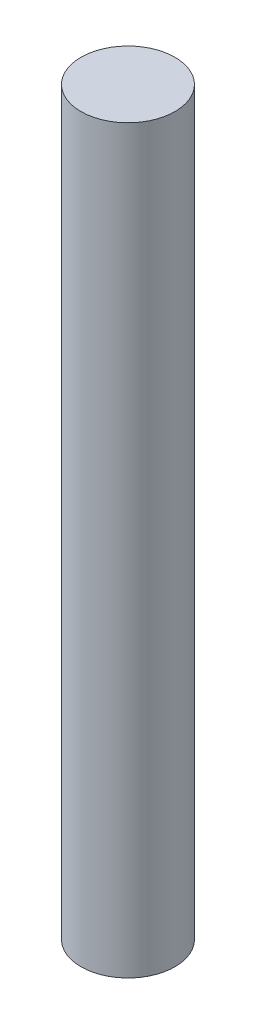
SolidWorks part; units mm, degrees
ref_plane "Front Plane" through (0, 0, 0) normal (0, 0, 1) x (1, 0, 0)
ref_plane "Top Plane" through (0, 0, 0) normal (0, 1, 0) x (1, 0, 0)
ref_plane "Right Plane" through (0, 0, 0) normal (1, 0, 0) x (0, 0, -1)
sketch "Sketch1" plane through (0, 0, 0) normal (0, 1, 0) x (1, 0, 0)
  circle A0 centre (0, 0) radius 3.175
  dimension "D1" = 6.35
extrude "Boss-Extrude1" add sketch "Sketch1" along normal blind 50
